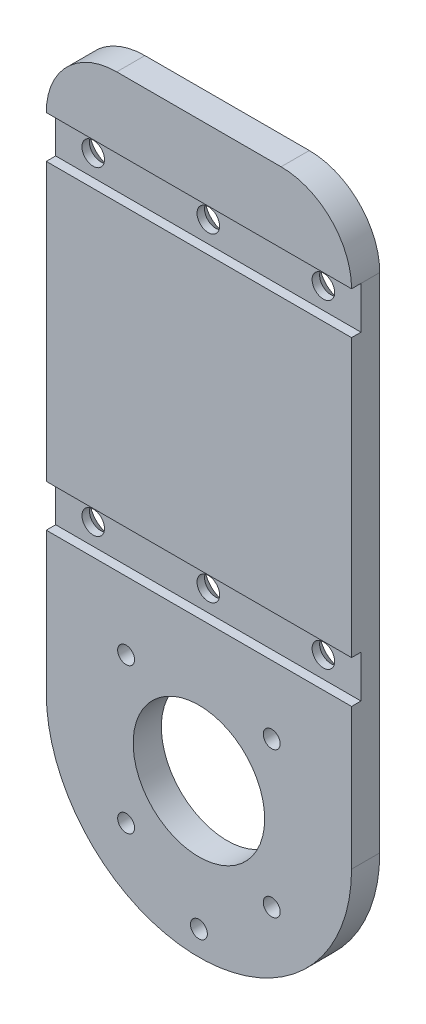
SolidWorks part; units mm, degrees
ref_plane "Front Plane" through (0, 0, 0) normal (0, 0, 1) x (1, 0, 0)
ref_plane "Top Plane" through (0, 0, 0) normal (0, 1, 0) x (1, 0, 0)
ref_plane "Right Plane" through (0, 0, 0) normal (1, 0, 0) x (0, 0, -1)
sketch "Sketch1" plane through (0, 0, 0) normal (0, 0, 1) x (1, 0, 0)
  line L1 (-32.5, -95) -> (32.5, -95)
  line L2 (-32.5, -95) -> (-32.5, 95)
  line L3 (-32.5, 95) -> (32.5, 95)
  line L4 (32.5, -95) -> (32.5, 95)
  line L5 (-32.5, -95) -> (32.5, 95) construction
  line L6 (-32.5, 95) -> (32.5, -95) construction
  line L7 (15.5, -110.5) -> (-15.5, -110.5)
  line L8 (15.5, -110.5) -> (15.5, -79.5)
  line L9 (15.5, -79.5) -> (-15.5, -79.5)
  line L10 (-15.5, -110.5) -> (-15.5, -79.5)
  line L11 (15.5, -110.5) -> (-15.5, -79.5) construction
  line L12 (15.5, -79.5) -> (-15.5, -110.5) construction
  circle A0 centre (0, -95) radius 32.5
  circle A1 centre (0, -95) radius 42 construction
  circle A2 centre (0, -95) radius 14
  point P0 (0, 0)
  point P14 (0, -127.5)
  dimension "D1" = 84
  dimension "D4" = 28
  dimension "D2" = 31
  dimension "D3" = 31
  dimension "D5" = 65
  dimension "D6" = 190
  dimension "D7" = 222.5
extrude "Boss-Extrude1" add sketch "Sketch1" along normal blind 6 contours A0 L4 L3 L2 | L1 A0 L10 L9 L8 | L1 A0 L8 L7 L10 | A2 L1 L10 L7 L8 | A2 L1 L8 L9 L10 region at (0, -78.7429, 0) region at (0, 12.6028, 0) region at (0, -111.2571, 0) region at (-15.1534, -87.25, 0) region at (-14.75, -95.3466, 0)
hole_wizard "M3 Clearance Hole1" positions "Sketch2" profile "Sketch3" hole size "M3" standard "ANSI Metric"
sketch "Sketch2" plane through (0, 0, 0) normal (0, 0, -1) x (-1, 0, 0)
  point P0 (-15.5, -110.5)
  point P3 (15.5, -110.5)
  point P6 (15.5, -79.5)
  point P9 (-15.5, -79.5)
sketch "Sketch3" plane through (15.5, -110.5, 0) normal (1, 0, 0) x (0, 1, 0)
  line L0 (0, 0) -> (0, 7.0815)
  line L1 (0, 7.0815) -> (1.8, 6)
  line L2 (1.8, 6) -> (1.8, 0)
  line L5 (1.8, 0) -> (0, 0)
  line L10 (0, 7.0815) -> (-1.8, 6) construction
  line L11 (0, -6.35) -> (0, 107.95) construction
  dimension "Hole Dia." = 3.6
  dimension "Hole Depth" = 6
  dimension "Drill Angle" = 118
fillet "Fillet1" radius 15 2 edges at (-32.5, 95, 3) (32.5, 95, 3)
sketch "Sketch4" plane through (0, 0, 6) normal (0, 0, 1) x (1, 0, 0)
  line L0 (32.5, -95) -> (32.5, 80) construction
  line L1 (32.5, -65) -> (-32.5, -65)
  line L2 (32.5, -65) -> (32.5, -56)
  line L3 (32.5, -56) -> (-32.5, -56)
  line L4 (-32.5, -65) -> (-32.5, -56)
  line L5 (-32.5, -95) -> (-32.5, 80) construction
  line L6 (0, 12) -> (0, 3)
  line L7 (32.5, 80) -> (-32.5, 80)
  line L8 (32.5, 80) -> (32.5, 71)
  line L9 (32.5, 71) -> (-32.5, 71)
  line L10 (-32.5, 80) -> (-32.5, 71)
  line L11 (-32.5, 12) -> (32.5, 12)
  line L12 (-32.5, 12) -> (-32.5, 3)
  line L13 (-32.5, 3) -> (32.5, 3)
  line L14 (32.5, 12) -> (32.5, 3)
  point P20 (0, 7.5)
  line M15 (-32.5, 80) -> (-32.5, -95)
  line M17 (32.5, -95) -> (32.5, 80)
  dimension "D1" = 9
  dimension "D2" = 9
  dimension "D3" = 9
  dimension "D4" = 30
  dimension "D5" = 127
  dimension "D6" = 63.5
extrude "Cut-Extrude1" cut sketch "Sketch4" against normal blind 2 contours L9 L7 M17 M15 | L13 L6 L11 M15 | L6 L13 L11 M17 | L3 L1 M17 M15 region at (0, -60.5, 6) region at (16.25, 7.5, 6) region at (-16.25, 7.5, 6) region at (0, 75.5, 6)
hole_wizard "M4 Clearance Hole1" positions "Sketch5" profile "Sketch6" hole size "M4" standard "ANSI Metric"
sketch "Sketch5" plane through (0, 0, 4) normal (0, 0, 1) x (1, 0, 0)
  line L0 (-32.5, 75.5) -> (32.5, 75.5)
  line L1 (-32.5, 80) -> (-32.5, 71) construction
  line L2 (32.5, 71) -> (32.5, 80) construction
  line L4 (-32.5, 7.5) -> (32.5, 7.5)
  line L5 (-32.5, 12) -> (-32.5, 3) construction
  line L6 (32.5, 3) -> (32.5, 12) construction
  line L8 (-32.5, -60.5) -> (32.5, -60.5)
  line L9 (-32.5, -56) -> (-32.5, -65) construction
  line L10 (32.5, -65) -> (32.5, -56) construction
  point P24 (-24.5, 75.5)
  point P26 (24.5, 75.5)
  point P28 (0, 75.5)
  point P30 (-24.5, 7.5)
  point P32 (0, 7.5)
  point P34 (24.5, 7.5)
  point P36 (24.5, -60.5)
  point P38 (0, -60.5)
  point P40 (-24.5, -60.5)
  dimension "D1" = 8
  dimension "D2" = 8
sketch "Sketch6" plane through (-24.5, -60.5, 4) normal (1, 0, 0) x (0, -1, 0)
  line L0 (0, 0) -> (0, 7.4421)
  line L1 (0, 7.4421) -> (2.4, 6)
  line L2 (2.4, 6) -> (2.4, 0)
  line L5 (2.4, 0) -> (0, 0)
  line L10 (0, 7.4421) -> (-2.4, 6) construction
  line L11 (0, -6.35) -> (0, 107.95) construction
  dimension "Hole Dia." = 4.8
  dimension "Hole Depth" = 6
  dimension "Drill Angle" = 118
chamfer "Chamfer1" distance 2.4 13 edges at (13.7, -110.5, 0) (-17.3, -110.5, 0) (-17.3, -79.5, 0) (13.7, -79.5, 0) (-22.1, 75.5, 0) (2.4, 75.5, 0) (26.9, 75.5, 0) (26.9, 7.5, 0) (2.4, 7.5, 0) (-22.1, 7.5, 0) (-22.1, -60.5, 0) (2.4, -60.5, 0) (26.9, -60.5, 0)
sketch "Sketch7" plane through (0, 0, 6) normal (0, 0, 1) x (1, 0, 0)
  line L0 (32.5, 12) -> (32.5, 71) construction
  line L1 (-32.5, 27) -> (32.5, 27)
  line L2 (-32.5, 27) -> (-32.5, 105)
  line L3 (-32.5, 105) -> (32.5, 105)
  line L4 (32.5, 27) -> (32.5, 105)
  line L5 (-17.5, 95) -> (17.5, 95) construction
  line L6 (-32.5, 12) -> (-32.5, 71) construction
  line L7 (-32.5, 12) -> (32.5, 12) construction
  dimension "D1" = 10
  dimension "D2" = 15
extrude "Cut-Extrude3" cut sketch "Sketch7" against normal through all
fillet "Fillet2" radius 15 2 edges at (32.5, 27, 3) (-32.5, 27, 3)
sketch "Sketch8" plane through (0, 0, 0) normal (0, 0, 1) x (1, 0, 0)
  line L0 (0, -109) -> (0, -127.5) construction
  circle A0 centre (0, -122.3) radius 5
  circle A1 centre (0, -95) radius 14 construction
  arc A2 (-32.5, -95) -> (32.5, -95) centre (0, -95) ccw construction
  point P0 (0, -122.3)
  dimension "D1" = 10
  dimension "D2" = 5.2
hole_wizard "CSK for M3 Flat Head Machine Screw1" positions "Sketch8" profile "Sketch9" countersink size "M3" standard "ANSI Metric"
sketch "Sketch9" plane through (0, -122.3, 0) normal (1, 0, 0) x (0, 1, 0)
  line L0 (0, 0) -> (0, 21.0815)
  line L1 (0, 21.0815) -> (1.8, 20)
  line L2 (1.8, 20) -> (1.8, 1.35)
  line L3 (1.8, 1.35) -> (3.15, 0)
  line L5 (3.15, 0) -> (0, 0)
  line L6 (-1.8, 1.35) -> (-3.15, 0) construction
  line L10 (0, 21.0815) -> (-1.8, 20) construction
  line L11 (0, -6.35) -> (0, 107.95) construction
  dimension "Hole Dia." = 3.6
  dimension "Hole Depth" = 20
  dimension "Near C'Sink Dia." = 6.3
  dimension "Near C'Sink Angle" = 90
  dimension "Drill Angle" = 118
